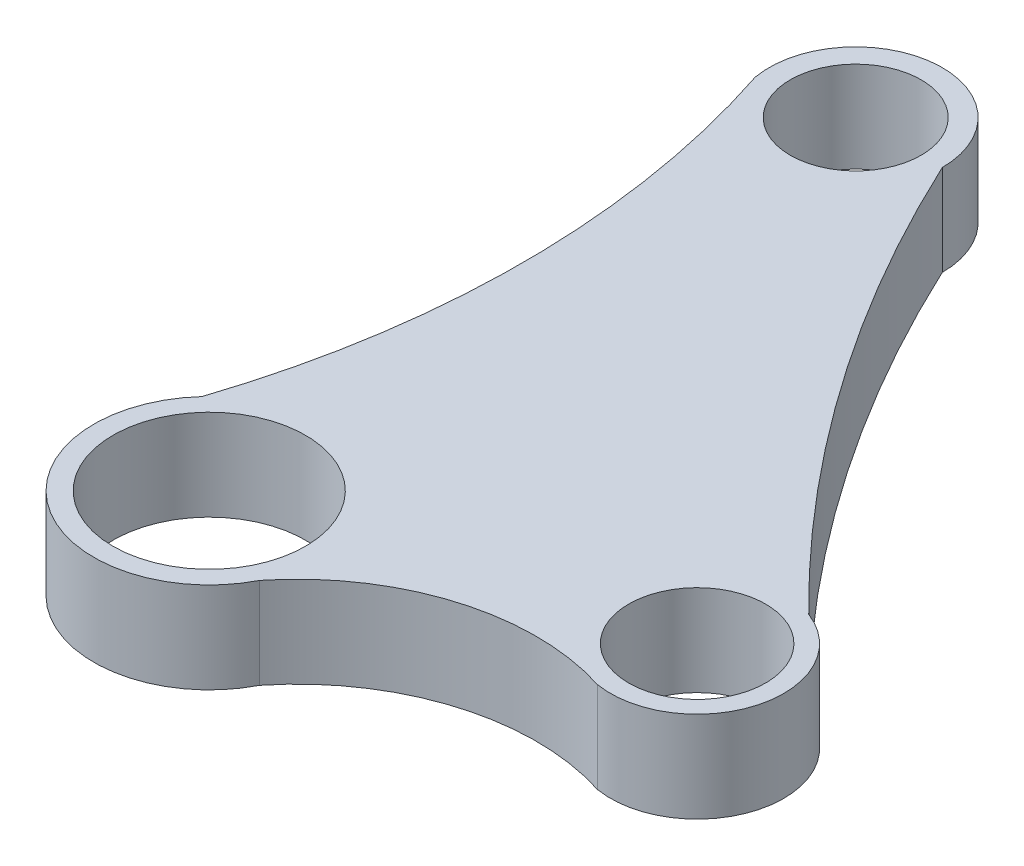
SolidWorks part; units mm, degrees
ref_plane "Front Plane" through (0, 0, 0) normal (0, 0, 1) x (1, 0, 0)
ref_plane "Top Plane" through (0, 0, 0) normal (0, 1, 0) x (1, 0, 0)
ref_plane "Right Plane" through (0, 0, 0) normal (1, 0, 0) x (0, 0, -1)
sketch "Sketch1" plane through (0, 0, 0) normal (0, 1, 0) x (1, 0, 0)
  circle A0 centre (0, 0) radius 12.7
  circle A1 centre (0, 71.12) radius 9.525
  circle A2 centre (41.3969, 12.2805) radius 9.525
  arc A3 (-9.3771, 69.4481) -> (-9.3771, 8.565) centre (-101.5678, 39.0066) cw
  arc A4 (9.525, 71.12) -> (44.7607, 21.1918) centre (165.9685, 144.129) ccw
  arc A5 (11.3158, -5.7657) -> (39.8358, 2.8843) centre (31.8611, -22.164) cw
  circle A6 centre (0, 71.12) radius 7.1995
  circle A7 centre (0, 0) radius 10.5879
  circle A8 centre (41.3969, 12.2805) radius 7.5318
  dimension "D1" = 19.05
  dimension "D2" = 25.4
  dimension "D3" = 19.05
  dimension "D5" = 43.18
  dimension ".8" = 71.12
extrude "Boss-Extrude1" add sketch "Sketch1" along normal blind 10 contours A0 A5 A2 A1 | A0 A7 | A1 A6 | A2 A8 region at (11.9998, 0, 2.8809) region at (13.385, 0, -31.2152) region at (-8.7411, 0, -68.3563) region at (32.7617, 0, -15.6123)
